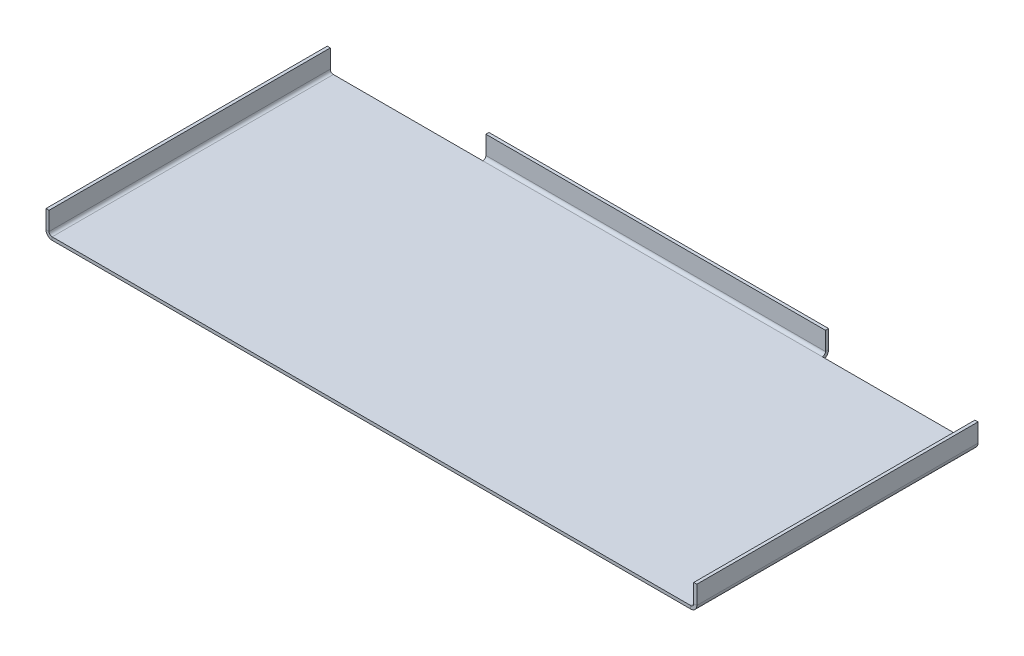
SolidWorks part; units mm, degrees
note: The reader was unsure of these and kept them because the rebuilt part matched: flange length of "Edge-Flange1", "Edge-Flange2".
material "6061-T6 (SS)"
ref_plane "X-Y Datum" through (0, 0, 0) normal (0, 0, 1) x (1, 0, 0)
ref_plane "X-Z Datum" through (0, 0, 0) normal (0, 1, 0) x (1, 0, 0)
ref_plane "Y-Z Datum" through (0, 0, 0) normal (1, 0, 0) x (0, 0, -1)
sketch "Sketch1" plane through (0, 0, 0) normal (0, 1, 0) x (1, 0, 0)
  line L1 (0, 0) -> (673.1102, 0)
  line L2 (0, 0) -> (0, 290.83)
  line L3 (0, 290.83) -> (673.1102, 290.83)
  line L4 (673.1102, 0) -> (673.1102, 290.83)
base flange "Base-Flange1" sketch "Sketch1" thickness 3.175 reverse thickness direction no parameters "D1"=3.175
edge flange "Edge-Flange1" sketch "Sketch8" flange angle 90 flange length 25.4 flange position bend outside bend radius 3.175 thickness 3.175 relief rectangular parameters "D6"=10
sketch "Sketch8" plane through (0, 0, -290.83) normal (0, 0, -1) x (-1, 0, 0)
  line L0 (-336.5551, 0) -> (-336.5551, 57.9221) construction
  line L3 (-512.1795, 22.225) -> (-160.9307, 22.225)
  line L7 (-160.9307, 22.225) -> (-160.9307, 0)
  line L11 (-673.1102, 0) -> (0, 0) construction
  line L12 (-512.1795, 0) -> (-160.9307, 0)
  line L17 (-512.1795, 22.225) -> (-512.1795, 0)
bend "EdgeBend1" bend radius 3.175 bend angle 90 parameters "D5"=1
edge flange "Edge-Flange2" sketch "Sketch13" flange profiles "Sketch13", "Sketch14" flange angle 90 flange length 25.4 flange position material inside bend radius 3.175 thickness 3.175 relief rectangular parameters "D6"=10, "D8"=1
sketch "Sketch13" plane through (673.1102, 0, 0) normal (1, 0, 0) x (0, 0, -1)
  line L2 (0, 0) -> (0, 22.225)
  line L3 (0, 22.225) -> (290.83, 22.225)
  line L4 (290.83, 22.225) -> (290.83, 0)
  line L7 (0, 0) -> (290.83, 0) construction
  line L8 (0, 0) -> (290.83, 0)
sketch "Sketch14" plane through (0, 0, 0) normal (-1, 0, 0) x (0, 0, 1)
  line L2 (0, 0) -> (0, 22.225)
  line L3 (0, 22.225) -> (-290.83, 22.225)
  line L4 (-290.83, 22.225) -> (-290.83, 0)
  line L5 (-290.83, 0) -> (0, 0) construction
  line L6 (-290.83, 0) -> (0, 0)
bend "EdgeBend2" bend radius 3.175 bend angle 90 parameters "D5"=2
bend "EdgeBend3" bend radius 3.175 bend angle 90 parameters "D5"=3
sketch "Bend-Lines1" [suppressed] plane through (0, 0, 0) normal (0, 1, 0) x (1, 0, 0)
sketch "Bounding-Box1" [suppressed] plane through (0, 0, 0) normal (0, 1, 0) x (1, 0, 0)
sheet metal parameters "Sheet-Metal1" thickness 3.175 parameters "D1"=9.525
flat pattern "Flat-Pattern1" [suppressed]
sketch "Bend-Lines2" plane through (0, 0, 0) normal (0, 1, 0) x (1, 0, 0)
sketch3d "Bounding-Box2" [suppressed]
  line L0 (673.1102, 290.83, 0) -> (0, 290.83, 0) construction
  line L1 (673.1102, 0, 0) -> (0, 0, 0) construction
  line L2 (673.1102, 290.83, 0) -> (673.1102, 0, 0) construction
  line L3 (0, 290.83, 0) -> (0, 0, 0) construction
sheet metal parameters "Sheet-Metal2" thickness 3.175 parameters "D1"=9.525
flat pattern "Flat-Pattern1"
sketch "Bend-Lines2" plane through (0, 0, 0) normal (0, 1, 0) x (1, 0, 0)
  line L0 (673.1102, 294.5705) -> (0, 294.5705) construction
  line L1 (673.1102, 294.5705) -> (0, 294.5705) construction
sketch3d "Bounding-Box2" [suppressed]
  line L0 (673.1102, 317.3609, 0) -> (0, 317.3609, 0) construction
  line L1 (673.1102, 0, 0) -> (0, 0, 0) construction
  line L2 (673.1102, 317.3609, 0) -> (673.1102, 0, 0) construction
  line L3 (0, 317.3609, 0) -> (0, 0, 0) construction
bend of the flat pattern "Flatten-<EdgeBend1>1"
sheet metal parameters "Sheet-Metal3" thickness 3.175 parameters "D1"=9.525
flat pattern "Flat-Pattern1"
sketch "Bend-Lines2" plane through (0, 0, 0) normal (0, 1, 0) x (1, 0, 0)
  line L0 (512.1795, 294.5705) -> (160.9307, 294.5705) construction
  line L1 (512.1795, 294.5705) -> (160.9307, 294.5705) construction
  line L2 (2.6095, 290.83) -> (2.6095, 0) construction
  line L3 (670.5006, 0) -> (670.5006, 290.83) construction
  line L4 (2.6095, 290.83) -> (2.6095, 0) construction
  line L5 (670.5006, 0) -> (670.5006, 290.83) construction
sketch3d "Bounding-Box2" [suppressed]
  line L0 (693.2911, 317.3609, 0) -> (-20.1809, 317.3609, 0) construction
  line L1 (693.2911, 0, 0) -> (-20.1809, 0, 0) construction
  line L2 (693.2911, 317.3609, 0) -> (693.2911, 0, 0) construction
  line L3 (-20.1809, 317.3609, 0) -> (-20.1809, 0, 0) construction
bend of the flat pattern "Flatten-<EdgeBend1>1"
bend of the flat pattern "Flatten-<EdgeBend2>1"
bend of the flat pattern "Flatten-<EdgeBend3>1"
